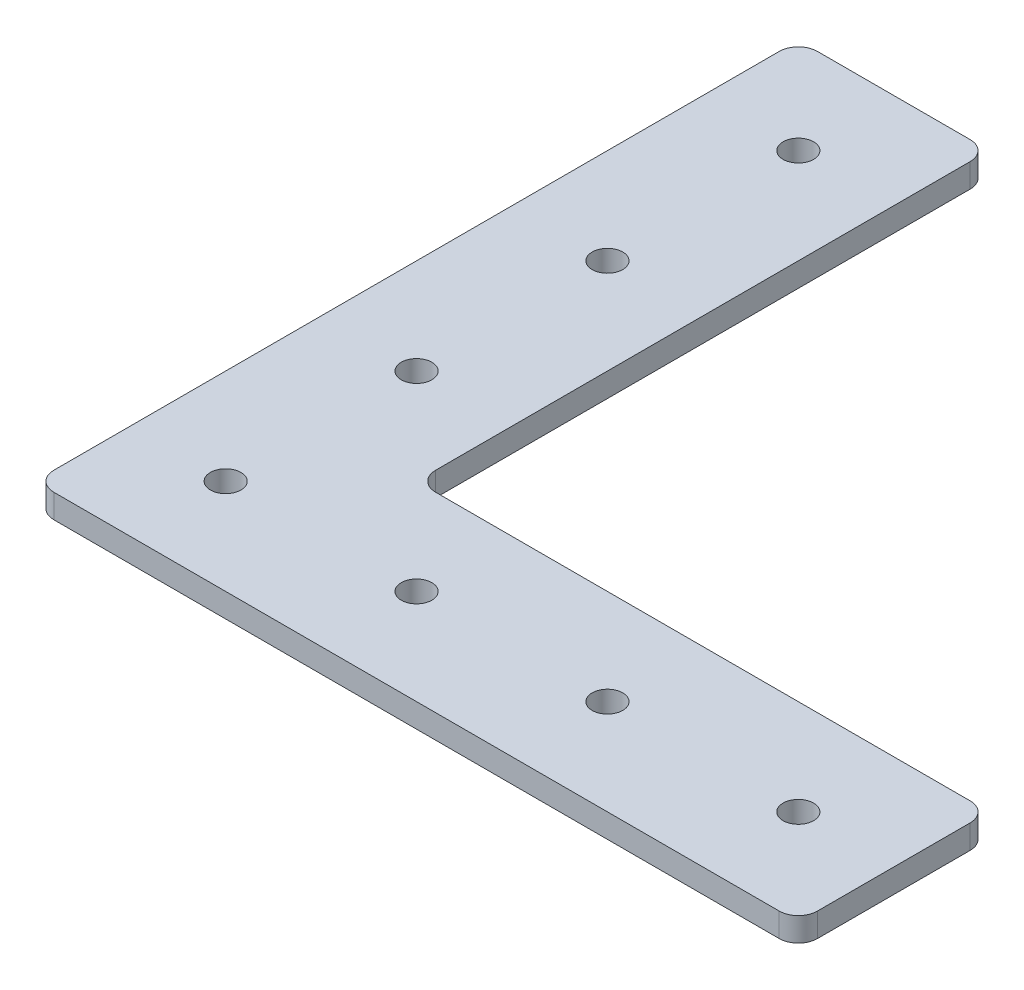
SolidWorks part; units mm, degrees
material "1060 Alloy"
ref_plane "Front Plane" through (0, 0, 0) normal (0, 0, 1) x (1, 0, 0)
ref_plane "Top Plane" through (0, 0, 0) normal (0, 1, 0) x (1, 0, 0)
ref_plane "Right Plane" through (0, 0, 0) normal (1, 0, 0) x (0, 0, -1)
sketch "Sketch1" plane through (0, 0, 0) normal (0, 1, 0) x (1, 0, 0)
  line L1 (2.54, 0) -> (25.4, 0)
  line L2 (0, 2.54) -> (0, 99.06)
  line L3 (2.54, 101.6) -> (22.86, 101.6)
  line L4 (25.4, 27.94) -> (25.4, 99.06)
  line L5 (0, 0) -> (99.06, 0)
  line L6 (0, 0) -> (0, 25.4)
  line L7 (27.94, 25.4) -> (99.06, 25.4)
  line L8 (101.6, 2.54) -> (101.6, 22.86)
  circle A0 centre (12.7, 12.7) radius 2.032
  circle A1 centre (38.1, 12.7) radius 2.032
  circle A2 centre (63.5, 12.7) radius 2.032
  circle A3 centre (88.9, 12.7) radius 2.032
  circle A4 centre (12.7, 38.1) radius 2.032
  circle A5 centre (12.7, 63.5) radius 2.032
  circle A6 centre (12.7, 88.9) radius 2.032
  arc A7 (0, 2.54) -> (2.54, 0) centre (2.54, 2.54) ccw
  arc A8 (99.06, 0) -> (101.6, 2.54) centre (99.06, 2.54) ccw
  arc A9 (101.6, 22.86) -> (99.06, 25.4) centre (99.06, 22.86) ccw
  arc A10 (27.94, 25.4) -> (25.4, 27.94) centre (27.94, 27.94) cw
  arc A11 (25.4, 99.06) -> (22.86, 101.6) centre (22.86, 99.06) ccw
  arc A12 (0, 99.06) -> (2.54, 101.6) centre (2.54, 99.06) cw
  point P28 (101.6, 0)
  point P31 (101.6, 25.4)
  point P36 (25.4, 101.6)
  point P39 (0, 101.6)
  dimension "D5" = 4.064
  dimension "D6" = 4.064
  dimension "D7" = 4.064
  dimension "D8" = 4.064
  dimension "D9" = 12.7
  dimension "D10" = 12.7
  dimension "D11" = 25.4
  dimension "D12" = 12.7
  dimension "D13" = 25.4
  dimension "D14" = 12.7
  dimension "D15" = 25.4
  dimension "D16" = 12.7
  dimension "D17" = 4.064
  dimension "D18" = 25.4
  dimension "D19" = 4.064
  dimension "D20" = 25.4
  dimension "D21" = 4.064
  dimension "D22" = 25.4
  dimension "D23" = 12.7
  dimension "D24" = 12.7
  dimension "D25" = 12.7
  dimension "D26" = 2.54
  dimension "D1" = 101.6
  dimension "D2" = 101.6
  dimension "D3" = 25.4
  dimension "D4" = 25.4
extrude "Boss-Extrude1" add sketch "Sketch1" along normal blind 3.175 contours A12 L2 A7 L1 L5 A8 L8 A9 L7 A10 L4 A11 L3 A6 A5 A4 A3 A2 A1 A0 region at (1.7599, 0, -1.7599)
